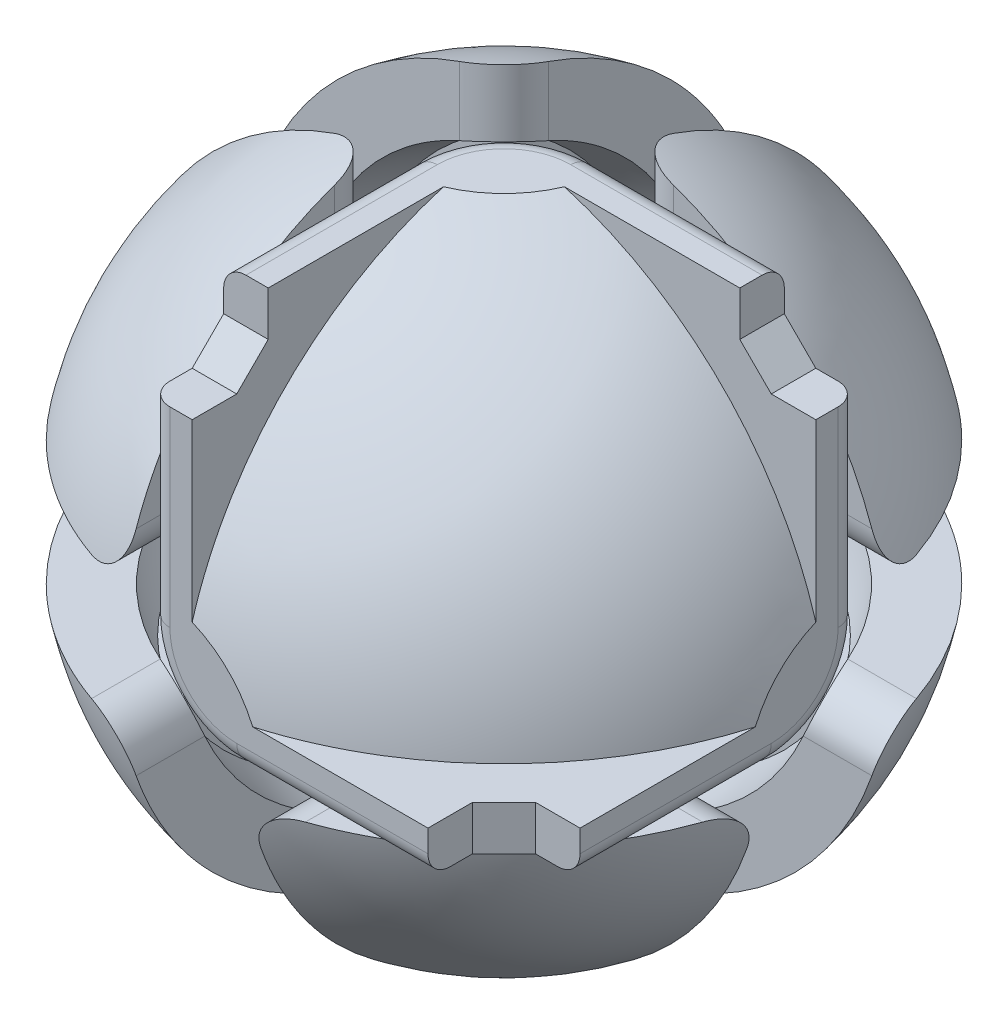
SolidWorks part; units mm, degrees
ref_plane "Front Plane" through (0, 0, 0) normal (1, 0, 0) x (0, 1, 0)
ref_plane "Top Plane" through (0, 0, 0) normal (0, 0, 1) x (0, 1, 0)
ref_plane "Right Plane" through (0, 0, 0) normal (0, 1, 0) x (-1, 0, 0)
sketch "Sketch1" plane through (0, 0, 0) normal (1, 0, 0) x (0, 1, 0)
  line L0 (0, 37) -> (0, -37)
  arc A0 (0, -37) -> (0, 37) centre (0, 0) ccw
  dimension "D1" = 74
revolve "Revolve1" add sketch "Sketch1" angle 360 about L0
sketch "Sketch2" plane through (0, 0, 0) normal (1, 0, 0) x (0, 1, 0)
  line L0 (0, 0) -> (0, 37) construction
  line L1 (-7, 36.3318) -> (-7, 29.1719)
  line L2 (7, 36.3318) -> (7, 29.1719)
  line L5 (-12, 27.4955) -> (-12, 19.6214)
  line L6 (0, 0) -> (37, 0) construction
  line L7 (12, 27.4955) -> (12, 19.6214)
  arc A0 (12, 27.4955) -> (7, 29.1719) centre (0, 0) ccw
  arc A1 (12, 19.6214) -> (-12, 19.6214) centre (0, 0) ccw
  circle A2 centre (0, 0) radius 37 construction
  arc A3 (7, 36.3318) -> (-7, 36.3318) centre (0, 0) ccw
  arc A4 (-7, 29.1719) -> (-12, 27.4955) centre (0, 0) ccw
  dimension "D3" = 60
  dimension "D4" = 46
  dimension "D1" = 7
  dimension "D2" = 7
  dimension "D5" = 12
  dimension "D6" = 12
revolve "Cut-Revolve1" cut sketch "Sketch2" angle 360 about L6
sketch "Sketch3" plane through (0, 0, 0) normal (1, 0, 0) x (0, 1, 0)
  line L0 (0, 0) -> (0, 36.4522) construction
pattern_circular "CirPattern1" count 2 every 90 about axis through (0, 0, 0) along (0, 0, 1) of "Cut-Revolve1" reverse direction yes
sketch "Sketch5" plane through (0, 0, 0) normal (0, 1, 0) x (-1, 0, 0)
  line L0 (0, 0) -> (41.2324, 0) construction
pattern_circular "CirPattern2" count 2 every 90 about axis through (0, 0, 0) along (-1, 0, 0) of "Cut-Revolve1" reverse direction yes
sketch "Sketch6" plane through (0, 0, 0) normal (0, 0, 1) x (0, 1, 0)
  line L1 (0, 0) -> (40, 0)
  line L2 (0, 0) -> (0, -40)
  line L3 (0, -40) -> (40, -40)
  line L4 (40, 0) -> (40, -40)
  dimension "D1" = 40
  dimension "D2" = 40
extrude "Boss-Extrude1" add sketch "Sketch6" along normal blind 40
fillet "Fillet2" [suppressed] radius 5
fillet "Fillet3" [suppressed] radius 2.5
sketch "Sketch7" plane through (0, 0, 0) normal (0, -1, 0) x (1, 0, 0)
  line L1 (98.3669, 42) -> (7, 42)
  line L2 (0, 42) -> (0, 0) construction
  line L3 (7, 42) -> (7, 41.4126)
  line L4 (7, 35.6511) -> (7, 7) construction
  line L5 (42, 0) -> (98.3669, 0)
  line L6 (98.3669, 0) -> (98.3669, 42)
  arc A0 (42, 0) -> (7, 41.4126) centre (0, 0) ccw
  dimension "D1" = 84
revolve "Cut-Revolve5" cut sketch "Sketch7" angle 90 about L2 reverse direction yes
sketch "Sketch8" plane through (0, 0, 0) normal (0, -1, 0) x (1, 0, 0)
  line L0 (40, 12.8062) -> (40, 0) construction
  line L1 (0, 0) -> (40, 0)
  line L2 (0, 0) -> (0, 40)
  line L3 (0, 40) -> (31.4645, 40)
  line L4 (40, 0) -> (40, 31.4645)
  line L5 (0, 40) -> (12.8062, 40) construction
  line L6 (31.4645, 40) -> (31.4645, 35)
  line L7 (31.4645, 35) -> (35, 31.4645)
  line L8 (35, 31.4645) -> (40, 31.4645)
  dimension "D1" = 5
  dimension "D2" = 135
extrude "Boss-Extrude2" add sketch "Sketch8" against normal blind 5
sketch "Sketch9" plane through (0, 0, 0) normal (0, 0, -1) x (1, 0, 0)
  line L0 (40, 0) -> (40, -12.8062) construction
  line L1 (0, 0) -> (40, 0)
  line L2 (0, 0) -> (0, -40)
  line L3 (0, -40) -> (31.4645, -40)
  line L4 (40, 0) -> (40, -31.4645)
  line L5 (12.8062, -40) -> (0, -40) construction
  line L6 (31.4645, -40) -> (31.4645, -35)
  line L7 (31.4645, -35) -> (35, -31.4645)
  line L8 (35, -31.4645) -> (40, -31.4645)
  dimension "D1" = 5
  dimension "D2" = 135
extrude "Boss-Extrude3" add sketch "Sketch9" against normal blind 5
sketch "Sketch10" plane through (0, 0, 0) normal (-1, 0, 0) x (0, -1, 0)
  line L0 (-12.8062, 40) -> (0, 40) construction
  line L1 (0, 0) -> (-40, 0)
  line L2 (0, 0) -> (0, 40)
  line L3 (0, 40) -> (-31.4645, 40)
  line L4 (-40, 0) -> (-40, 31.4645)
  line L5 (-40, 12.8062) -> (-40, 0) construction
  line L6 (-31.4645, 40) -> (-31.4645, 35)
  line L7 (-31.4645, 35) -> (-35, 31.4645)
  line L8 (-35, 31.4645) -> (-40, 31.4645)
  dimension "D1" = 5
  dimension "D2" = 135
extrude "Boss-Extrude4" add sketch "Sketch10" against normal blind 5
fillet "Fillet4" radius 10 3 edges at (0, 31.5, 0) (31.5, 0, 0) (0, 0, 31.5)
fillet "Fillet5" radius 2.5 9 edges at (20.7322, 40, 0) (0, 40, 20.7322) (40, 0, 20.7322) (40, 20.7322, 0) (0, 20.7322, 40) (2.9289, 2.9289, 40) (2.9289, 40, 2.9289) (40, 2.9289, 2.9289) (20.7322, 0, 40)
fillet "Fillet6" radius 5 21 edges at (7, -7, -31.9853) (7, -7, 31.9853) (7, -31.9853, 7) (-7, 31.9853, 7) (-7, -31.9853, 7) (-7, 7, -31.9853) (-7, 7, 31.9853) (-31.9853, 7, 7) (-7, -7, -31.9853) (-7, -7, 31.9853) (-31.9853, -7, 7) (31.9853, -7, 7) (7, 7, -31.9853) (-31.9853, 7, -7) (31.9853, 7, -7) (7, 31.9853, -7) (7, -31.9853, -7) (-7, -31.9853, -7) (-7, 31.9853, -7) (-31.9853, -7, -7) (31.9853, -7, -7)
